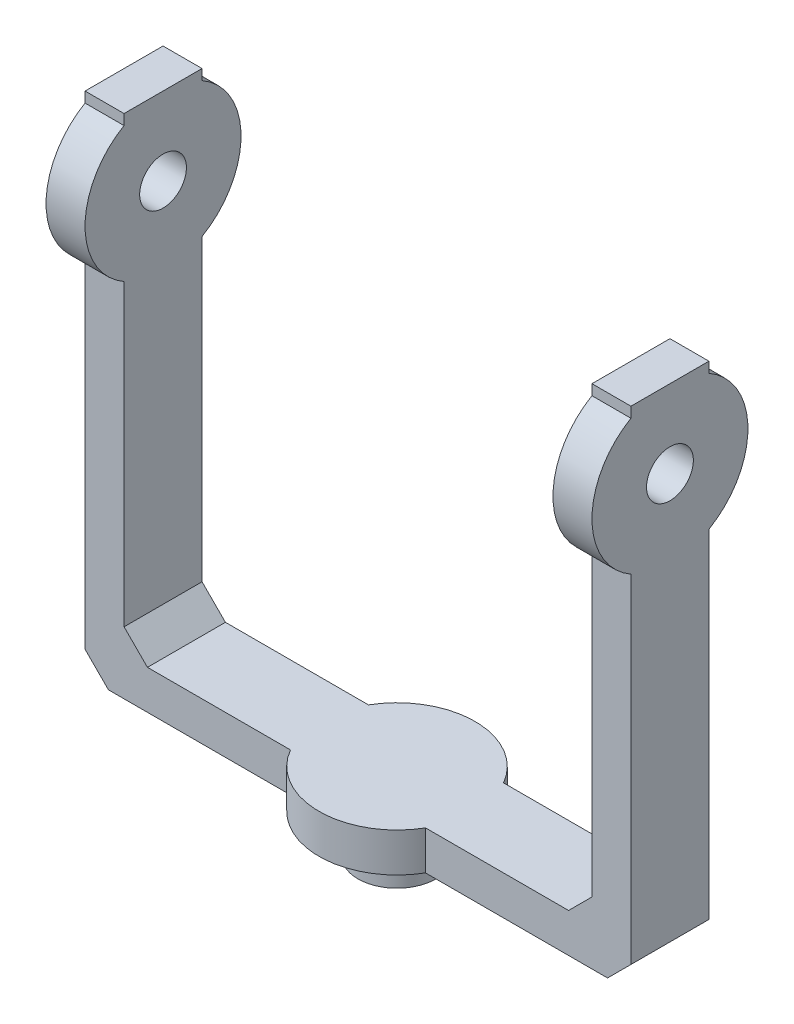
SolidWorks part; units mm, degrees
ref_plane "Front" through (0, 0, 0) normal (0, 0, 1) x (1, 0, 0)
ref_plane "Top" through (0, 0, 0) normal (0, 1, 0) x (1, 0, 0)
ref_plane "Right" through (0, 0, 0) normal (1, 0, 0) x (0, 0, -1)
sketch "Sketch1" plane through (0, 0, 0) normal (0, 1, 0) x (1, 0, 0)
  circle A0 centre (0, 0) radius 250
  dimension "D1" = 500
extrude "Boss-Extrude1" add sketch "Sketch1" along normal blind 250
sketch "Sketch2" plane through (0, 250, 0) normal (0, 1, 0) x (1, 0, 0)
  line L0 (-433.0127, 250) -> (-1500, 250)
  line L1 (0, 0) -> (-1500, 0) construction
  line L2 (1500, 250) -> (433.0127, 250)
  line L3 (1500, 250) -> (1500, -250)
  line L4 (1500, -250) -> (433.0127, -250)
  line L5 (-1500, 250) -> (-1500, -250)
  line L6 (1500, 250) -> (-307.8617, -51.3103) construction
  line L7 (1500, -250) -> (-1500, 250) construction
  line L8 (-433.0127, -250) -> (-1500, -250)
  arc A0 (-433.0127, -250) -> (433.0127, -250) centre (0, 0) ccw
  arc A1 (433.0127, 250) -> (-433.0127, 250) centre (0, 0) ccw
  dimension "D2" = 500
  dimension "D3" = 3000
extrude "Boss-Extrude2" add sketch "Sketch2" along normal blind 250
ref_plane "Plane1" through (0, 250, 0) normal (0, 1, 0) x (1, 0, 0)
sketch "Sketch4" plane through (0, 250, 0) normal (0, 1, 0) x (1, 0, 0)
  line L1 (1500, 250) -> (1750, 250)
  line L2 (1500, 250) -> (1500, -250)
  line L3 (1500, -250) -> (1750, -250)
  line L4 (1750, 250) -> (1750, -250)
  dimension "D1" = 250
  dimension "D2" = 500
extrude "Boss-Extrude3" add sketch "Sketch4" along normal blind 3250
ref_plane "Plane2" through (1500, 0, 0) normal (-1, 0, 0) x (0, 0, 1)
sketch "Sketch7" plane through (1500, 0, 0) normal (-1, 0, 0) x (0, 0, 1)
  line L0 (250, 3500) -> (-250, 3500) construction
  circle A0 centre (0, 3000) radius 500
  dimension "D1" = 1000
  dimension "D2" = 500
extrude "Boss-Extrude4" add sketch "Sketch7" against normal blind 250
sketch "Sketch8" plane through (1500, 0, 0) normal (-1, 0, 0) x (0, 0, 1)
  circle A0 centre (0, 3000) radius 150
extrude "Cut-Extrude1" cut sketch "Sketch8" against normal blind 250
mirror "Mirror1" about plane through (0, 0, 0) normal (1, 0, 0) of "Boss-Extrude3", "Boss-Extrude4", "Cut-Extrude1"
chamfer "Chamfer1" distance 150 angle 45 4 edges at (1750, 250, 0) (1500, 500, 0) (-1750, 250, 0) (-1500, 500, 0)
equation "\"BaseDiameter\"= .5"
equation "\"D1@Sketch1\"=\"BaseDiameter\""
equation "\"BaseHeight\"=0.25"
equation "\"D1@Boss-Extrude1\"=\"BaseHeight\""
equation "\"topdiameter\"=1"
equation "\"D1@Sketch2\"=\"topdiameter\""
equation "\"topheight\"=0.25"
equation "\"D1@Boss-Extrude2\"=\"topheight\""
